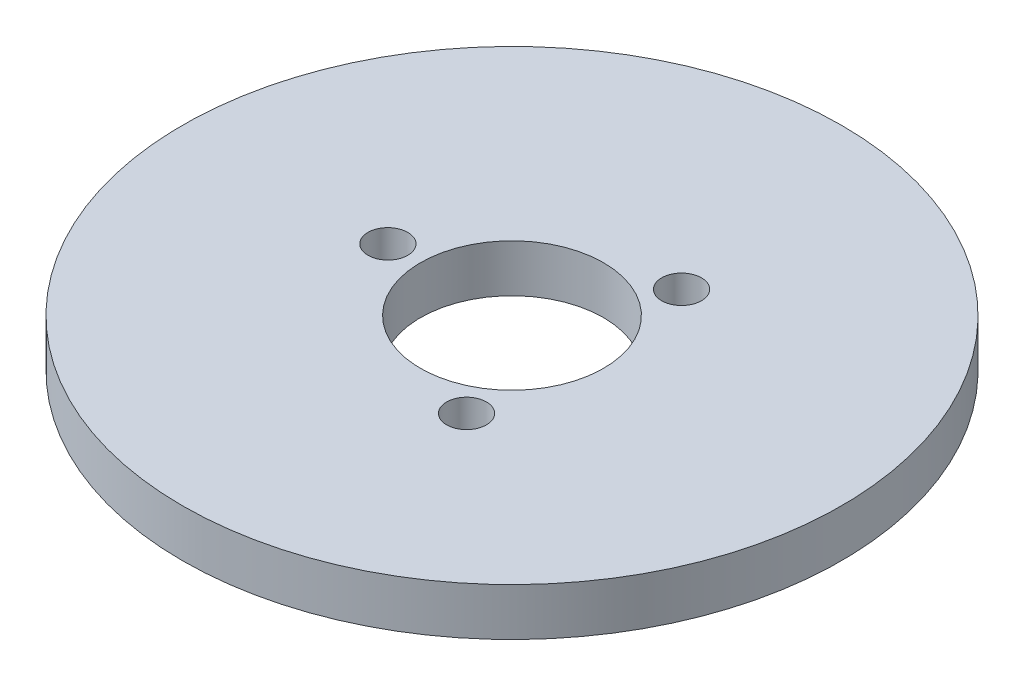
SolidWorks part; units mm, degrees
ref_plane "Front Plane" through (0, 0, 0) normal (0, 0, 1) x (1, 0, 0)
ref_plane "Top Plane" through (0, 0, 0) normal (0, 1, 0) x (1, 0, 0)
ref_plane "Right Plane" through (0, 0, 0) normal (1, 0, 0) x (0, 0, -1)
sketch "Sketch1" plane through (0, 0, 0) normal (0, 1, 0) x (1, 0, 0)
  circle A0 centre (0, 0) radius 90
  dimension "FLANGE_OD" = 180
extrude "Boss-Extrude1" add sketch "Sketch1" along normal blind 13
sketch "Sketch2" plane through (0, 0, 0) normal (0, 1, 0) x (1, 0, 0)
  circle A0 centre (0, 0) radius 25
  dimension "BORE_D" = 50
extrude "Cut-Extrude1" cut sketch "Sketch2" along normal through all
sketch "Sketch3" plane through (0, 13, 0) normal (0, 1, 0) x (1, 0, 0)
  circle A0 centre (0, 0) radius 33.8968 construction
  circle A1 centre (-33.8968, 0) radius 5.4342
  dimension "BOLT_D" = 10.8684
  dimension "BOLT_PCD" = 67.7935
extrude "Cut-Extrude2" cut sketch "Sketch3" against normal blind 11.9675
pattern_circular "CirPattern1" count 3 over 360 about axis through (0, 0, 0) along (0, 1, 0) of "Cut-Extrude2"
